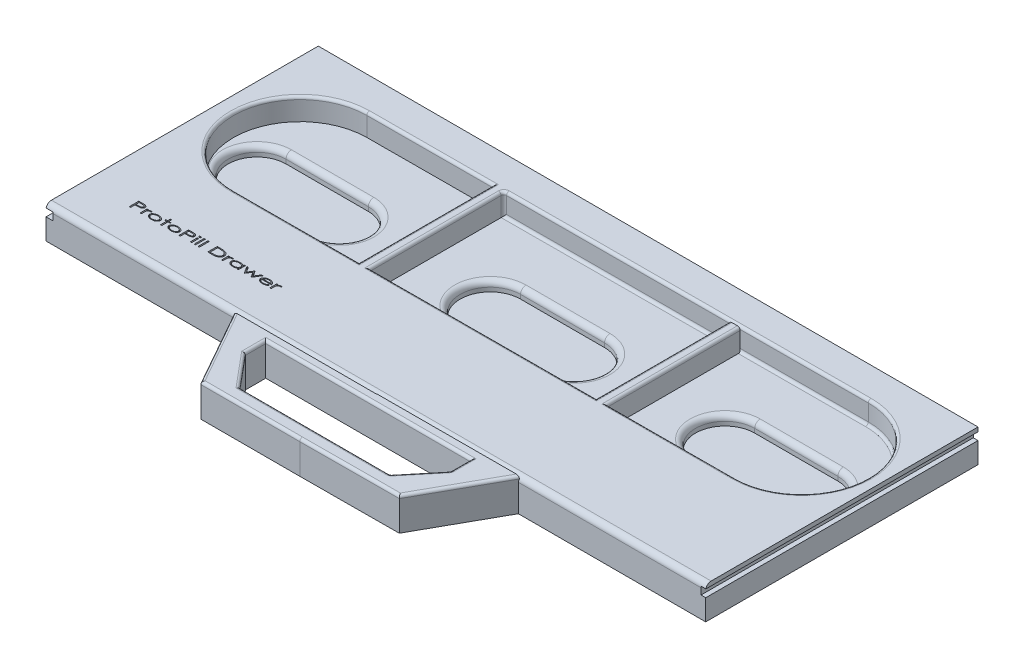
SolidWorks part; units mm, degrees
ref_plane "Front Plane" through (0, 0, 0) normal (0, 0, 1) x (1, 0, 0)
ref_plane "Top Plane" through (0, 0, 0) normal (0, 1, 0) x (1, 0, 0)
ref_plane "Right Plane" through (0, 0, 0) normal (1, 0, 0) x (0, 0, -1)
sketch "Sketch1" plane through (0, 0, 0) normal (0, 1, 0) x (1, 0, 0)
  line L2 (2.2154, -28.3198) -> (244.3174, -28.3198)
  line L4 (244.3174, 64.6802) -> (2.2154, 64.6802)
  line L6 (244.3174, 64.6802) -> (244.3174, -28.3198)
  line L7 (2.2154, 64.6802) -> (2.2154, -28.3198)
  dimension "D2" = 93
extrude "Boss-Extrude1" add sketch "Sketch1" along normal blind 12
sketch "Sketch3" plane through (0, 12, 0) normal (0, 1, 0) x (1, 0, 0)
  line L0 (37.1381, -19.9605) -> (-7.858, -19.9605) construction
  line L2 (37.1381, -19.9605) -> (37.1381, -24.4605) construction
  line L4 (37.1381, -19.9605) -> (123.1941, -19.9579) construction
  line L5 (123.6473, -19.9605) -> (210.1566, -19.9605) construction
  line L6 (210.1566, -19.9605) -> (210.1566, -24.4605) construction
  line L7 (123.6473, -19.9605) -> (123.6473, -24.4605) construction
  line L8 (37.1381, -19.9605) -> (37.1381, 7.1502) construction
  line L9 (123.6473, -19.9605) -> (123.6473, 8.5509) construction
  line L10 (210.1566, -19.9605) -> (210.1566, 7.8884) construction
  line L11 (0.0174, -19.9605) -> (247.1649, -19.9605)
  circle A2 centre (123.7727, -8.9393) radius 11.15
  circle A3 centre (37.3245, -8.6421) radius 11.15
  circle A4 centre (209.8985, -8.6813) radius 11.15
  dimension "D2" = 22.3
  dimension "D3" = 22.3
  dimension "D4" = 22.3
sketch "Sketch2" plane through (0, 0, 28.3198) normal (0, 0, 1) x (1, 0, 0)
  line L0 (0, 10.4529) -> (0, 7.6902)
  line L2 (0, 7.6902) -> (4.6941, 7.6902)
  line L3 (4.6941, 7.6902) -> (4.6941, 10.4529)
  line L5 (4.6941, 10.4529) -> (0, 10.4529)
extrude "Cut-Extrude1" cut sketch "Sketch2" against normal through all
ref_plane "Plane1" through (123.6473, 0, 0) normal (1, 0, 0) x (0, 0, -1)
mirror "Mirror5" about plane through (123.6473, 0, 0) normal (1, 0, 0) of "Cut-Extrude1"
sketch "Sketch7" plane through (0, 0, 28.3198) normal (0, 0, 1) x (1, 0, 0)
sketch "Sketch8" plane through (0, 0, 28.3198) normal (0, 0, 1) x (1, 0, 0)
  line L10 (244.3174, 10.4529) -> (244.3174, 12)
  line L14 (244.3174, 12) -> (2.2154, 12)
  line L17 (244.3174, 10.4529) -> (244.3174, 12)
  line L18 (2.2154, 12) -> (2.2154, 10.4529)
  line L19 (2.2154, 10.4529) -> (4.6941, 10.4529)
  line L20 (4.6941, 10.4529) -> (4.6941, 7.6902)
  line L21 (4.6941, 7.6902) -> (2.2154, 7.6902)
  line L22 (2.2154, 7.6902) -> (2.2154, 0)
  line L23 (2.2154, 0) -> (244.3174, 0)
  line L34 (2.2154, 12) -> (2.2154, 10.4529)
  line L35 (2.2154, 10.4529) -> (4.6941, 10.4529)
  line L36 (4.6941, 10.4529) -> (4.6941, 7.6902)
  line L37 (4.6941, 7.6902) -> (2.2154, 7.6902)
  line L38 (2.2154, 7.6902) -> (2.2154, 0)
  line L39 (2.2154, 0) -> (244.3174, 0)
  line L60 (244.3174, 12) -> (2.2154, 12)
  line L65 (244.3174, 0) -> (244.3174, 7.6902)
  line L66 (244.3174, 0) -> (244.3174, 7.6902)
  line L67 (244.3174, 7.6902) -> (242.6006, 7.6902)
  line L68 (244.3174, 7.6902) -> (242.6006, 7.6902)
  line L69 (242.6006, 7.6902) -> (242.6006, 10.4529)
  line L70 (242.6006, 7.6902) -> (242.6006, 10.4529)
  line L71 (242.6006, 10.4529) -> (244.3174, 10.4529)
  line L72 (242.6006, 10.4529) -> (244.3174, 10.4529)
  dimension "D1" = 0
extrude "Boss-Extrude3" add sketch "Sketch8" along normal blind 53
sketch "Sketch9" plane through (0, 12, 0) normal (0, 1, 0) x (1, 0, 0)
  line L0 (32.277, -18.0846) -> (215.6701, -17.457) construction
  line L3 (32.193, 6.4621) -> (215.5861, 7.0898)
  line L4 (32.361, -42.6314) -> (215.7541, -42.0037)
  arc A0 (32.193, 6.4621) -> (32.361, -42.6314) centre (32.277, -18.0846) ccw
  arc A1 (215.7541, -42.0037) -> (215.5861, 7.0898) centre (215.6701, -17.457) ccw
  point P6 (123.9735, -17.7708)
extrude "Cut-Extrude2" cut sketch "Sketch9" against normal blind 8
sketch "Sketch10" plane through (0, 4, 0) normal (0, 1, 0) x (1, 0, 0)
  line L0 (22.2559, -23.9029) -> (52.4711, -23.9029) construction
  line L1 (22.2559, -13.2713) -> (52.4711, -13.2713)
  line L2 (22.2559, -34.5345) -> (52.4711, -34.5345)
  line L3 (108.2536, -24.2865) -> (139.0697, -24.2865) construction
  line L4 (108.2536, -13.2003) -> (139.0697, -13.2003)
  line L5 (108.2536, -35.3728) -> (139.0697, -35.3728)
  line L6 (193.8044, -23.6865) -> (224.3383, -23.6865) construction
  line L7 (193.8044, -12.8155) -> (224.3383, -12.8155)
  line L8 (193.8044, -34.5575) -> (224.3383, -34.5575)
  arc A0 (22.2559, -13.2713) -> (22.2559, -34.5345) centre (22.2559, -23.9029) ccw
  arc A1 (52.4711, -34.5345) -> (52.4711, -13.2713) centre (52.4711, -23.9029) ccw
  arc A2 (108.2536, -13.2003) -> (108.2536, -35.3728) centre (108.2536, -24.2865) ccw
  arc A3 (139.0697, -35.3728) -> (139.0697, -13.2003) centre (139.0697, -24.2865) ccw
  arc A4 (193.8044, -12.8155) -> (193.8044, -34.5575) centre (193.8044, -23.6865) ccw
  arc A5 (224.3383, -34.5575) -> (224.3383, -12.8155) centre (224.3383, -23.6865) ccw
  point P2 (37.3635, -23.9029)
  point P9 (123.6616, -24.2865)
  point P16 (209.0714, -23.6865)
extrude "Cut-Extrude4" cut sketch "Sketch10" against normal blind 3.5
fillet "Fillet2" radius 2 1 edges at (123.2664, 12, 81.3198)
fillet "Fillet3" radius 2 12 edges at (235.2093, 4, 23.6865) (209.0714, 4, 34.5575) (182.9335, 4, 23.6865) (150.1559, 4, 24.2865) (123.6616, 4, 35.3728) (97.1674, 4, 24.2865) (63.1027, 4, 23.9029) (37.3635, 4, 34.5345) (11.6243, 4, 23.9029) (209.0714, 4, 12.8155) (123.6616, 4, 13.2003) (37.3635, 4, 13.2713)
sketch "Sketch11" plane through (0, 12, 0) normal (0, 1, 0) x (1, 0, 0)
  line L0 (2.2154, 18.6064) -> (244.3174, 18.6064)
  line L1 (2.2154, 64.6802) -> (2.2154, -79.3198) construction
  line L2 (244.3174, -79.3198) -> (244.3174, 64.6802) construction
  line L3 (244.3174, 18.6064) -> (244.3174, 64.6802)
  line L4 (244.3174, 64.6802) -> (2.2154, 64.6802)
  line L5 (2.2154, 64.6802) -> (2.2154, 18.6064)
extrude "Cut-Extrude5" cut sketch "Sketch11" against normal through all
sketch "Sketch12" plane through (0, 0, 0) normal (0, -1, 0) x (1, 0, 0)
  circle A0 centre (79.2049, -2.6546) radius 3.025
  circle A2 centre (79.2049, 6.3419) radius 3.025
  circle A10 centre (169.8585, 5.9307) radius 3.025
  circle A11 centre (169.8585, -2.6546) radius 3.025
extrude "Cut-Extrude6" cut sketch "Sketch12" against normal blind 2
sketch "Sketch13" plane through (0, 12, 0) normal (0, 1, 0) x (1, 0, 0)
  text T0 "ProtoPill Drawer" font "Century Gothic" height 3.5
extrude "Cut-Extrude7" cut sketch "Sketch13" against normal blind 2
sketch "Sketch14" plane through (0, 0, 0) normal (0, -1, 0) x (1, 0, 0)
  line L0 (76.1475, 6.1393) -> (79.1725, 12.8178)
  line L1 (79.1725, 12.8178) -> (82.1975, 6.1393)
  line L2 (82.1975, 6.1393) -> (76.1475, 6.1393)
  line L3 (76.1475, -2.8572) -> (79.1725, -9.5356)
  line L4 (79.1725, -9.5356) -> (82.1975, -2.8572)
  line L5 (82.1975, -2.8572) -> (76.1475, -2.8572)
  line L6 (166.8011, 5.7281) -> (169.8261, 12.4066)
  line L7 (169.8261, 12.4066) -> (172.8511, 5.7281)
  line L8 (172.8511, 5.7281) -> (166.8011, 5.7281)
  line L9 (166.8011, -2.8572) -> (169.8261, -9.5356)
  line L10 (169.8261, -9.5356) -> (172.8511, -2.8572)
  line L11 (172.8511, -2.8572) -> (166.8011, -2.8572)
extrude "Cut-Extrude8" cut sketch "Sketch14" against normal blind 2
sketch "Sketch15" plane through (0, 12, 0) normal (0, 1, 0) x (1, 0, 0)
  line L2 (146.7092, -47.8489) -> (134.6091, -54.4141)
  line L3 (146.7092, -47.8489) -> (146.7092, -74.4208)
  line L4 (146.7092, -74.4208) -> (134.6091, -67.8555)
sketch "Sketch18" plane through (0, 12, 0) normal (0, 1, 0) x (1, 0, 0)
  line L0 (123.2664, 18.6064) -> (123.6473, -144.7634) construction
  line L3 (2.2154, 18.6064) -> (244.3174, 18.6064) construction
  line L5 (123.6473, -81.3198) -> (71.3, -81.3198)
  line L6 (242.6006, -81.3198) -> (4.6941, -81.3198) construction
  line L7 (71.3, -81.3198) -> (87.2174, -109.5296)
  line L8 (87.2174, -109.5296) -> (123.5652, -109.5296)
  line L9 (159.9126, -109.3601) -> (123.5652, -109.5296)
  line L10 (175.6982, -81.0763) -> (159.9126, -109.3601)
  line L11 (71.3, -81.3198) -> (175.6982, -81.0763)
extrude "Boss-Extrude5" add sketch "Sketch18" against normal blind 12 contours L0 L5 L7 L8 | L11 L0 L9 L10 region at (145.8907, 12, 94.445) region at (101.1571, 12, 94.583)
sketch "Sketch19" plane through (0, 12, 0) normal (0, 1, 0) x (1, 0, 0)
  line L0 (71.3, -81.3198) -> (73.898, -85.9241)
  line L1 (71.3, -81.3198) -> (87.2174, -109.5296) construction
  line L2 (123.6473, -6.6) -> (123.6473, 6.6) construction
  line L4 (86.1365, -92.0529) -> (86.1365, -84.6047)
  line L5 (86.1365, -84.6047) -> (161.3312, -84.6047)
  line L6 (161.3312, -92.0872) -> (161.3312, -84.6047)
  line L7 (86.1365, -92.0529) -> (161.3312, -84.6047) construction
  line L8 (86.1365, -84.6047) -> (161.3312, -92.0872) construction
  line L9 (86.1365, -92.0529) -> (96.2211, -104.1307)
  line L10 (96.2211, -104.1307) -> (151.3789, -104.1307)
  line L11 (151.3789, -104.1307) -> (161.3312, -92.0872)
  point P5 (123.6473, -88.3373)
extrude "Cut-Extrude9" cut sketch "Sketch19" against normal blind 23 contours L6 L5 L4 region at (123.7565, 12, 93.8527)
fillet "Fillet6" radius 1 14 edges at (123.8, 0, 104.1307) (161.3312, 0, 88.346) (123.8, 12, 104.1307) (156.355, 0, 98.109) (161.3312, 6, 92.0872) (156.355, 12, 98.109) (151.3789, 6, 104.1307) (123.7338, 12, 84.6047) (91.1788, 12, 98.0918) (86.1365, 12, 88.3288) (161.3312, 12, 88.346) (167.8054, 12, 95.2182) (105.3913, 12, 109.5296) (79.2587, 12, 95.4247)
sketch "Sketch20" plane through (0, 4, 0) normal (0, 1, 0) x (1, 0, 0)
  line L0 (65.1027, -23.9029) -> (95.173, -23.9029) construction
  line L2 (32.361, -42.6314) -> (215.7541, -42.0037) construction
  line L4 (78.2818, -42.4742) -> (82.2818, -42.4606)
  line L5 (82.2818, -42.4606) -> (82.2818, 6.6336)
  line L6 (215.5861, 7.0898) -> (32.193, 6.4621) construction
  line L7 (82.2818, 6.6336) -> (78.2818, 6.6199)
  line L8 (78.2818, 6.6199) -> (78.2818, -42.4742)
  arc A2 (52.4711, -36.5345) -> (52.4711, -11.2713) centre (52.4711, -23.9029) ccw construction
  arc A3 (108.2536, -11.2003) -> (108.2536, -37.3728) centre (108.2536, -24.2865) ccw construction
  point P8 (0, 0)
extrude "Boss-Extrude6" add sketch "Sketch20" along normal blind 8 contours L4 L5 L7 L8
mirror "Mirror6" about plane through (123.6473, 0, 0) normal (1, 0, 0) of "Boss-Extrude6"
fillet "Fillet7" radius 1 15 edges at (192.3835, 12, 42.0837) (240.2169, 12, 17.373) (192.3835, 4, 42.0837) (240.2169, 4, 17.373) (55.3214, 12, 42.5528) (7.7302, 12, 18.1686) (148.9339, 12, -6.8617) (148.9339, 4, -6.8617) (82.2818, 8, -6.6336) (169.0129, 12, 17.7719) (123.6473, 12, 42.319) (165.0129, 12, 17.7719) (55.2374, 12, -6.541) (78.2818, 12, 17.9272) (82.2818, 12, 17.9135)
